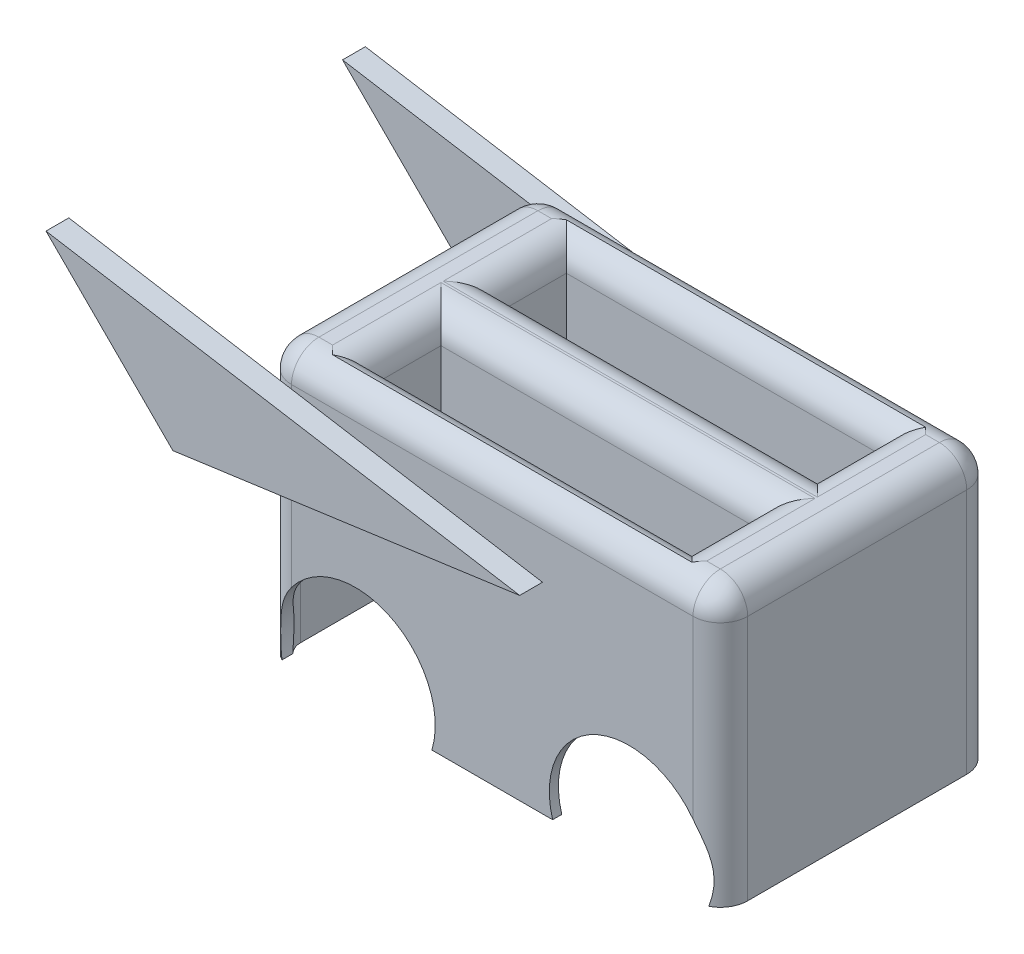
SolidWorks part; units mm, degrees
material "6061-T6 (SS)"
ref_plane "Front Plane" through (0, 0, 0) normal (0, 0, 1) x (1, 0, 0)
ref_plane "Top Plane" through (0, 0, 0) normal (0, 1, 0) x (1, 0, 0)
ref_plane "Right Plane" through (0, 0, 0) normal (1, 0, 0) x (0, 0, -1)
sketch "Sketch1" plane through (0, 0, 0) normal (0, 1, 0) x (1, 0, 0)
  line L0 (-127, 76.2) -> (-127, -76.2)
  line L1 (-127, 76.2) -> (127, 76.2)
  line L2 (-127, -76.2) -> (127, -76.2)
  line L3 (127, 76.2) -> (127, -76.2)
  line L4 (-127, 76.2) -> (127, -76.2) construction
  line L5 (-127, -76.2) -> (127, 76.2) construction
  point P1 (0, 0)
  dimension "D1" = 152.4
  dimension "D2" = 254
extrude "Boss-Extrude1" add sketch "Sketch1" along normal blind 152.4
sketch "Sketch2" plane through (0, 152.4, 0) normal (0, 1, 0) x (1, 0, 0)
  line L0 (0, 0) -> (-111.0728, 0) construction
  line L1 (-88.9, 53.975) -> (88.9, 53.975)
  line L2 (-88.9, 53.975) -> (-88.9, 15.875)
  line L3 (-88.9, 15.875) -> (88.9, 15.875)
  line L4 (88.9, 53.975) -> (88.9, 15.875)
  line L5 (-88.9, 53.975) -> (88.9, 15.875) construction
  line L6 (-88.9, 15.875) -> (88.9, 53.975) construction
  line L7 (-88.9, -15.875) -> (88.9, -15.875)
  line L8 (-88.9, -15.875) -> (-88.9, -53.975)
  line L9 (-88.9, -53.975) -> (88.9, -53.975)
  line L10 (88.9, -15.875) -> (88.9, -53.975)
  line L11 (-88.9, -15.875) -> (88.9, -53.975) construction
  line L12 (-88.9, -53.975) -> (88.9, -15.875) construction
  point P4 (0, 34.925)
  point P9 (0, -34.925)
  dimension "D1" = 177.8
  dimension "D2" = 38.1
  dimension "D3" = 31.75
extrude "Cut-Extrude1" cut sketch "Sketch2" against normal blind 63.5
fillet "Fillet1" radius 15.24 16 edges at (-88.9, 152.4, 34.925) (0, 152.4, 53.975) (88.9, 152.4, 34.925) (0, 152.4, 15.875) (88.9, 152.4, -34.925) (0, 152.4, -53.975) (0, 152.4, -15.875) (-88.9, 152.4, -34.925) (-127, 76.2, 76.2) (-127, 76.2, -76.2) (-127, 152.4, 0) (0, 152.4, 76.2) (127, 152.4, 0) (0, 152.4, -76.2) (127, 76.2, -76.2) (127, 76.2, 76.2)
shell "Shell4" thickness 5.08 removed face at (0, 0, 0)
sketch "Sketch3" plane through (0, 0, 76.2) normal (0, 0, 1) x (1, 0, 0)
  line L0 (-235.7671, 155.512) -> (27.9647, 111.7024)
  line L1 (27.9647, 111.7024) -> (-165.1115, 84.9628)
  line L2 (-165.1115, 84.9628) -> (-235.7671, 155.512)
extrude "Boss-Extrude2" add sketch "Sketch3" along normal blind 12.7
mirror "Mirror1" about plane through (0, 0, 0) normal (0, 0, 1) of "Boss-Extrude2"
sketch "Sketch4" plane through (0, 0, -76.2) normal (0, 0, -1) x (-1, 0, 0)
  line L0 (-111.76, 0) -> (111.76, 0) construction
  line L1 (-118.7971, 0) -> (-33.6029, 0)
  line L3 (33.6029, 0) -> (118.7971, 0)
  arc A0 (-118.7971, 0) -> (-33.6029, 0) centre (-76.2, 12.7) cw
  arc A1 (33.6029, 0) -> (118.7971, 0) centre (76.2, 12.7) cw
  point P9 (0, 0)
  point P10 (0, 0)
  dimension "D1" = 44.45
  dimension "D2" = 152.4
  dimension "D3" = 76.2
  dimension "D4" = 12.7
extrude "Cut-Extrude2" cut sketch "Sketch4" against normal through all
